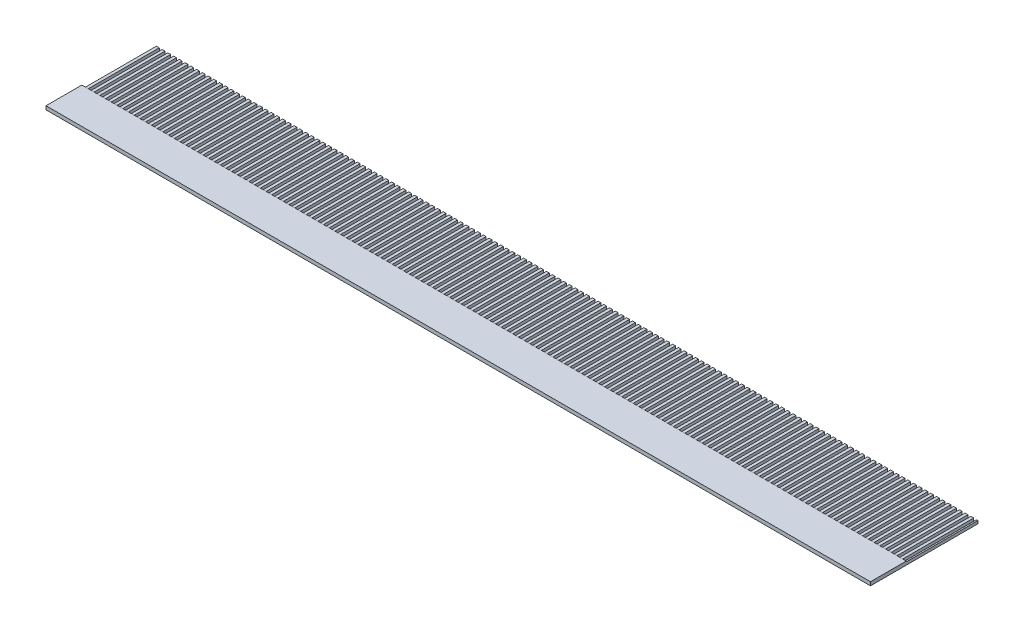
SolidWorks part; units mm, degrees
ref_plane "Front Plane" through (0, 0, 0) normal (0, 0, 1) x (1, 0, 0)
ref_plane "Top Plane" through (0, 0, 0) normal (0, 1, 0) x (1, 0, 0)
ref_plane "Right Plane" through (0, 0, 0) normal (1, 0, 0) x (0, 0, -1)
sketch "Sketch1" plane through (0, 0, 0) normal (0, 1, 0) x (1, 0, 0)
  line L1 (0, 0) -> (115, 0)
  line L2 (0, 0) -> (0, 15)
  line L3 (0, 15) -> (115, 15)
  line L4 (115, 0) -> (115, 15)
extrude "Boss-Extrude1" add sketch "Sketch1" along normal blind 0.5
sketch "Sketch2" plane through (0, 0.5, 0) normal (0, 1, 0) x (1, 0, 0)
  line L0 (115, 0) -> (115, 15) construction
  line L1 (0, 15) -> (115, 15)
  line L2 (0, 15) -> (0, 5)
  line L3 (0, 5) -> (115, 5)
  line L4 (115, 15) -> (115, 5)
extrude "Cut-Extrude1" cut sketch "Sketch2" against normal blind 0.1
sketch "Sketch3" plane through (0, 0.4, 0) normal (0, 1, 0) x (1, 0, 0)
  line L0 (0, 5) -> (115, 5) construction
  line L1 (0, 15) -> (0.4, 15)
  line L2 (0, 15) -> (0, 5)
  line L3 (0, 5) -> (0.4, 5)
  line L4 (0.4, 15) -> (0.4, 5)
extrude "Cut-Extrude2" cut sketch "Sketch3" against normal blind 0.4
pattern_linear "LPattern3" count 150 spacing 0.8 along (1, 0, 0) of "Cut-Extrude2"
